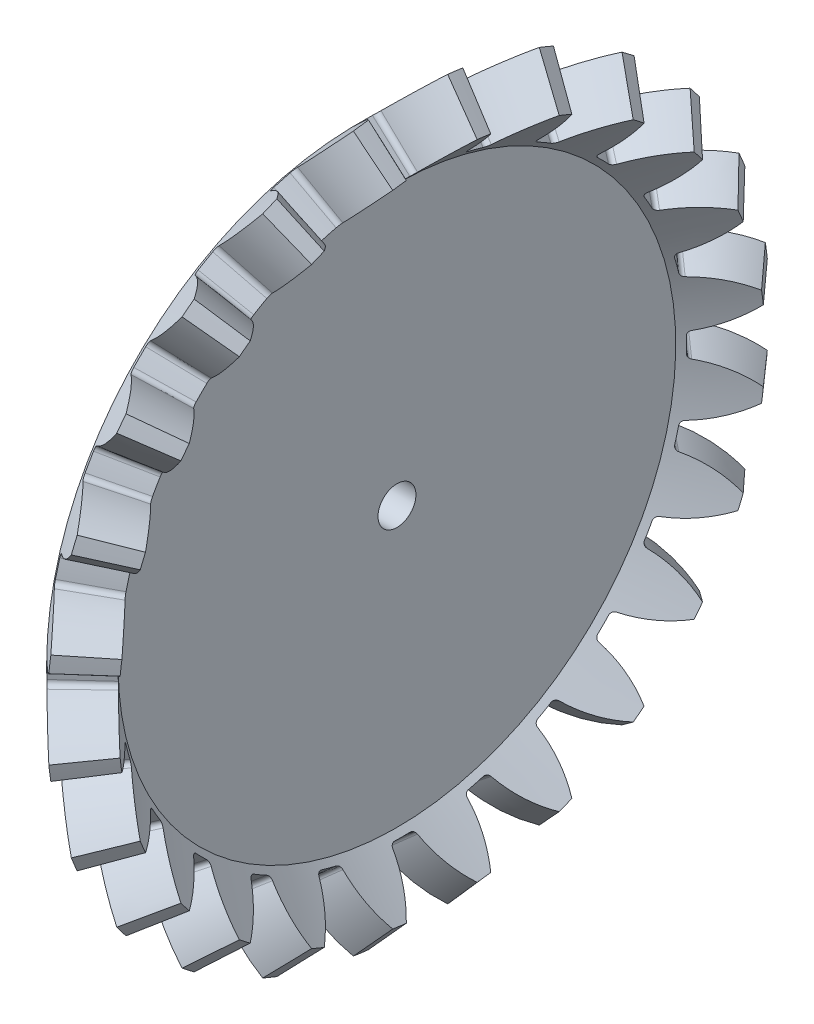
SolidWorks part; units mm, degrees
revolve "Base-Revolve" add sketch "BasProSke" angle 360 about L0 other way angle 7.5
sketch "BasProSke" plane through (0, 0, 0) normal (0, 1, 0) x (1, 0, 0)
  line L0 (-10, 0) -> (60, 0) construction
  line L1 (0, 0) -> (0, 24.6365)
  line L2 (0, 0) -> (3.076, 0)
  line L3 (3.076, 0) -> (3.076, 22.0557)
  line L4 (29.3635, 0) -> (-20.0585, 49.422) construction
  line L5 (0, 24.6365) -> (3.9545, 28.591)
  line L6 (29.3635, 0) -> (-44.1573, 82.7278) construction
  line L7 (29.3635, 0) -> (0, 24.6365) construction
  line L8 (3.9545, 28.591) -> (6.6163, 25.5959)
  line L9 (6.6163, 25.5959) -> (3.076, 22.0557)
  line L10 (2.3635, 27) -> (-9.6208, 27) construction
  dimension "D1" = 49.273
  dimension "D2" = 29.3635
  dimension "D3" = 38.1838
  dimension "D4" = 3.372
ref_plane "Plane1" through (0, 0, 0) normal (0, 0, 1) x (1, 0, 0)
ref_plane "Plane2" through (0, 0, 0) normal (0, 1, 0) x (1, 0, 0)
ref_plane "Plane3" through (0, 0, 0) normal (1, 0, 0) x (0, 0, -1)
other "Configuration Table"
sketch "HoldingSke" plane through (0, 0, 0) normal (0, 1, 0) x (1, 0, 0)
  line L0 (0, 0) -> (0.406, -0.1808)
  line L1 (-15, 0) -> (100, 0) construction
  line L2 (0, 0) -> (-90.9974, 40.8499)
  line L3 (0, 0) -> (-11.863, 4.5341)
  line L4 (0, 0) -> (7.8894, 3.5126)
  line L5 (0, 0) -> (-9.3695, -3.4946)
  line L6 (0, 0) -> (-10.5278, -7.1032)
  line L7 (-90.9974, 40.8499) -> (-84.6769, 69.5252)
  line L8 (-76.2, 2.25) -> (-75.7, 2.25)
  line L9 (-71.009, 38.7566) -> (-53.1078, 45.2721)
  line L10 (-76.2, 71.12) -> (104.1128, 71.12)
  line L11 (0, 0) -> (-4, 0)
  line L12 (-76.2, 101.6) -> (-76.123, 101.6)
  line L13 (24.9733, 27.94) -> (52.9518, 28.4284)
  line L14 (24.9733, 27.94) -> (24.9743, 27.94)
  line L15 (24.9733, 27.94) -> (100.4024, 29.5042)
  line L16 (-90.9974, 40.8499) -> (26.948, -11.6628)
  circle A0 centre (0, 0) radius 1.5
  circle A1 centre (0, 0) radius 5
  circle A2 centre (0, 0) radius 5
  circle A3 centre (0, 0) radius 1.5
  dimension "Num_teeth" = 24
  dimension "Pitch_radius" = 180.3128
  dimension "Width" = 4
ref_plane "ToothPln" through (1.9772, 26.6137, 0) normal (-0.7071, 0.7071, 0) x (0, 0, -1)
ref_plane "ToothPln2" through (14.6818, -14.6818, 0) normal (-0.7071, 0.7071, 0) x (0, 0, 1)
sketch "TooCutSke" plane through (1.9772, 26.6137, 0) normal (-0.7071, 0.7071, 0) x (0, 0, -1)
  line L2 (0, 26.4538) -> (221.7879, -1658.1923) construction
  line L3 (0, 26.4538) -> (119.7249, -1761.0552) construction
  line L4 (0, -15.621) -> (0, 105.791) construction
  line L6 (-24.765, -2.7963) -> (21.082, -2.7963) construction
  line L7 (3.5242, -0.3153) -> (1.8007, -0.4307) construction
  arc A0 (-3.5434, -3.1701) -> (3.5434, -3.1701) centre (0, 26.4538) ccw
  arc A1 (-0.6665, 2.1369) -> (0.6665, 2.1369) centre (0, 26.4538) ccw
  circle A2 centre (0, 26.4538) radius 27 construction
  circle A3 centre (0, 26.4538) radius 25.3717 construction
  arc A4 (1.0937, 1.7968) -> (0.6665, 2.1369) centre (0.6781, 1.713) ccw
  arc A5 (1.0937, 1.7968) -> (3.5434, -3.1701) centre (11.6808, 3.9308) ccw
  arc A6 (-3.5434, -3.1701) -> (-1.0937, 1.7968) centre (-11.6808, 3.9308) ccw
  arc A7 (-0.6665, 2.1369) -> (-1.0937, 1.7968) centre (-0.6781, 1.713) ccw
  ellipse E0 centre (0, 17.4206) end of major axis (28.591, 17.4206) minor radius 20.2169 construction
sketch "TooCutSke2" plane through (14.6818, -14.6818, 0) normal (-0.7071, 0.7071, 0) x (0, 0, 1)
  line L0 (0, 0) -> (0, 68.072) construction
  line L2 (21.082, 17.4206) -> (-20.32, 17.4206) construction
  circle A0 centre (0, 20.7631) radius 0.0127
  ellipse E1 centre (0, 0) end of major axis (-24.6365, 0) minor radius 17.4206 construction
loft "ToothCut" cut profiles "TooCutSke2", "TooCutSke"
pattern_circular "TeethCuts" count 24 every 15 about axis through (-10, 0, 0) along (1, 0, 0) of "ToothCut"
sketch "HubSke" plane through (0, 0, 0) normal (-1, 0, 0) x (0, 0, 1)
  circle A0 centre (0, 0) radius 5
  dimension "Diameter" = 10
extrude "Hub" add sketch "HubSke" along normal blind 0.0001
sketch "BorSke" plane through (0, 0, 0) normal (1, 0, 0) x (0, 0, -1)
  circle A0 centre (0, 0) radius 1.5
  dimension "Diameter" = 3
extrude "Bore" cut sketch "BorSke" along normal mid plane 58.7271
sketch "KeySke" plane through (0, 0, 0) normal (1, 0, 0) x (0, 0, -1)
  line L0 (-0.6, 0) -> (-0.6, 2)
  line L1 (-0.6, 2) -> (0.6, 2)
  line L2 (0.6, 2) -> (0.6, 0)
  line L3 (0, 0) -> (0, 34) construction
  line L4 (-0.6, 0) -> (0.6, 0)
  dimension "Offset" = 2
extrude "Keyway" [suppressed] cut sketch "KeySke" along normal mid plane 58.7271
pattern_circular "Keyway2" [suppressed] count 2 every 90 about axis through (-10, 0, 0) along (1, 0, 0)
equation "' \"Module@HoldingSke\" = 6.35"
equation "' \"Num_teeth@HoldingSke\" = 12"
equation "' \"Mating_teeth@HoldingSke\" = 12"
equation "' \"Ap@HoldingSke\" =  20"
equation "' \"Ap@HoldingSke\" = 20"
equation "' \"Width@HoldingSke\" = 0.5 * 25.4"
equation "' \"Hub_dia@HoldingSke\"= 2 * 25.4"
equation "' \"Hub_dia@HoldingSke\" = 2 * 25.4"
equation "' \"Mounting_dist@HoldingSke\" = 2 * 25.4"
equation "' \"Bore@HoldingSke\" = 19"
equation "' \"T_dim@HoldingSke\" = 0.1 * 25.4"
equation "' \"Width@KeySke\" = 0.25 * 25.4"
equation "' \"Show_teeth@HoldingSke\" = 100"
equation "' \"Backlash@HoldingSke\" = 0.009 * 25.4"
equation "' \"Addendum_fac@HoldingSke\" = 1.0"
equation "' \"Dedendum_fac@HoldingSke\" = 1.188"
equation "' \"Dedendum_add@HoldingSke\" = 0.002 * 25.4"
equation "' \"Clearance_fac@HoldingSke\" = 0.188"
equation "\"Pitch@HoldingSke\" = 1 / \"Module@HoldingSke\""
equation "' \"Addendum_fac@HoldingSke\" = 0.54 + 0.46 / (\"Num_teeth@HoldingSke\" /  \"Mating_teeth@HoldingSke\" ) ^ 2"
equation " \"Addendum_fac@HoldingSke\" = 2 - (0.54 + 0.46 / (\"Mating_teeth@HoldingSke\" /  \"Num_teeth@HoldingSke\" ) ^ 2)"
equation "\"Dedendum_fac@HoldingSke\" = 2.188 - \"Addendum_fac@HoldingSke\""
equation "\"Pitch_rad@BasProSke\" = \"Num_teeth@HoldingSke\" / \"Pitch@HoldingSke\" / 2"
equation "\"Pitch_ang@BasProSke\" = atn(\"Num_teeth@HoldingSke\" / \"Mating_teeth@HoldingSke\") * (180 / 3.14159265)"
equation "\"Addendum@BasProSke\" = \"Addendum_fac@HoldingSke\" / \"Pitch@HoldingSke\""
equation "\"Dedendum_plus@BasProSke\" = (\"Dedendum_fac@HoldingSke\" / \"Pitch@HoldingSke\" + \"Dedendum_add@HoldingSke\") * 1.25"
equation "\"Face_wid@BasProSke\" = \"Width@HoldingSke\""
equation "\"Radius@TooCutSke\" = ((\"Num_teeth@HoldingSke\" + 2 * \"Addendum_fac@HoldingSke\") / \"Pitch@HoldingSke\" ) / 2"
equation "\"Overcut_dia@TooCutSke\" =  1.02 * (\"Num_teeth@HoldingSke\" + 2 * \"Addendum_fac@HoldingSke\") / \"Pitch@HoldingSke\""
equation "\"Pitch_dia@TooCutSke\" = \"Num_teeth@HoldingSke\" / \"Pitch@HoldingSke\""
equation "\"Base_dia@TooCutSke\" = \"Num_teeth@HoldingSke\" / \"Pitch@HoldingSke\" * cos((\"Ap@HoldingSke\"  * 3.14159265 / 180))"
equation "'  \"Root_dia@TooCutSke\" =  (\"Num_teeth@HoldingSke\" + 2) / \"Pitch@HoldingSke\" - 2 * (\"Addendum_fac@HoldingSke\" + \"Dedendum_fac@HoldingSke\") / \"Pitch@HoldingSke\" - \"Dedendum_add@HoldingSke\" * 2"
equation "'  \"Root_dia@TooCutSke\" = (\"Num_teeth@HoldingSke\" + 2) / \"Pitch@HoldingSke\" - 2 * (\"Addendum_fac@HoldingSke\" + \"Dedendum_fac@HoldingSke\") / \"Pitch@HoldingSke\" - \"Dedendum_add@HoldingSke\" * 2"
equation "\"Root_dia@TooCutSke\" =  \"Num_teeth@HoldingSke\" / \"Pitch@HoldingSke\" -  2 * \"Dedendum_fac@HoldingSke\" / \"Pitch@HoldingSke\" - \"Dedendum_add@HoldingSke\" * 2"
equation "\"Half_ang@TooCutSke\" = 180 / \"Num_teeth@HoldingSke\""
equation "\"Half_CT@TooCutSke\" = \"Num_teeth@HoldingSke\" / \"Pitch@HoldingSke\" * sin((3.14159265 / 2 / \"Num_teeth@HoldingSke\")) / 2 - 2 * \"Backlash@HoldingSke\" / 4"
equation "\"Flank_rad@TooCutSke\" = \"Num_teeth@HoldingSke\" / \"Pitch@HoldingSke\" / 5"
equation "\"Root_fillet@TooCutSke\" = \"Clearance_fac@HoldingSke\" / \"Pitch@HoldingSke\" + \"Dedendum_add@HoldingSke\""
equation "\"Offset@ToothPln2\"  = \"Num_teeth@HoldingSke\" / \"Pitch@HoldingSke\" / 2 / sin(atn(\"Num_teeth@HoldingSke\" / \"Mating_teeth@HoldingSke\"))"
equation "\"Dedendum_plus@TooCutSke2\" = \"Dedendum_plus@BasProSke\""
equation "\"MHD@HoldingSke\" = \"Num_teeth@HoldingSke\" / \"Pitch@HoldingSke\" - 2 * \"Dedendum_plus@BasProSke\" * cos(atn(\"Num_teeth@HoldingSke\" / \"Mating_teeth@HoldingSke\"))"
equation "\"MBD@HoldingSke\" = \"Num_teeth@HoldingSke\" / \"Pitch@HoldingSke\" - 2 * \"Dedendum_plus@BasProSke\" * cos(atn(\"Num_teeth@HoldingSke\" / \"Mating_teeth@HoldingSke\")) - 0.002 * 25.4"
equation "\"MnMD@HoldingSke\" =  \"Num_teeth@HoldingSke\" / \"Pitch@HoldingSke\" / 2 / (\"Num_teeth@HoldingSke\" / \"Mating_teeth@HoldingSke\") + \"Dedendum_plus@BasProSke\" * sin(atn(\"Num_teeth@HoldingSke\" / \"Mating_teeth@HoldingSke\"))"
equation "\"OAL@HoldingSke\" = \"MnMD@HoldingSke\""
equation "\"MHD@HoldingSke\" = ((sgn( \"MHD@HoldingSke\" - \"Hub_dia@HoldingSke\" )-1)*( \"MHD@HoldingSke\" - \"Hub_dia@HoldingSke\" ))/-2+ \"Hub_dia@HoldingSke\""
equation "\"MBD@HoldingSke\" = ((sgn( \"MBD@HoldingSke\" - \"Bore@HoldingSke\" )-1)*( \"MBD@HoldingSke\" - \"Bore@HoldingSke\" ))/-2+ \"Bore@HoldingSke\""
equation "\"Face_wid@BasProSke\" = ((sgn( \"Face_wid@BasProSke\" - \"Offset@ToothPln2\" * 0.9)-1)*( \"Face_wid@BasProSke\" - \"Offset@ToothPln2\" * 0.9))/-2+ \"Offset@ToothPln2\" * 0.9"
equation "\"OAL@HoldingSke\" = ((sgn( \"OAL@HoldingSke\" - \"Mounting_dist@HoldingSke\" )+1)*( \"OAL@HoldingSke\" - \"Mounting_dist@HoldingSke\" ))/2 + \"Mounting_dist@HoldingSke\" + 0.000002 * 25.4"
equation "\"Num_teeth@TeethCuts\" = int( \"Show_teeth@HoldingSke\" ) + 1"
equation "\"Num_teeth@TeethCuts\" = ((sgn( \"Num_teeth@TeethCuts\" - \"Num_teeth@HoldingSke\" )-1)*( \"Num_teeth@TeethCuts\" - \"Num_teeth@HoldingSke\" ))/-2+ \"Num_teeth@HoldingSke\""
equation "\"Num_teeth@TeethCuts\" = ((sgn( \"Num_teeth@TeethCuts\" - 2.0)+1)*( \"Num_teeth@TeethCuts\" - 2.0))/2 +2.0"
equation "\"Angle@TeethCuts\" = 360.0 / \"Num_teeth@HoldingSke\""
equation "\"Diameter@HubSke\" = \"MHD@HoldingSke\""
equation "\"Length@Hub\" = \"OAL@HoldingSke\" - \"MnMD@HoldingSke\" + 0.000002 * 25.4"
equation "\"Diameter@BorSke\" = \"MBD@HoldingSke\""
equation "\"D1@Bore\" = \"OAL@HoldingSke\" * 2.0"
equation "\"D1@Keyway\" = \"OAL@HoldingSke\" * 2.0"
equation "\"Offset@KeySke\" = \"T_dim@HoldingSke\" + \"MBD@HoldingSke\" / 2.0"
